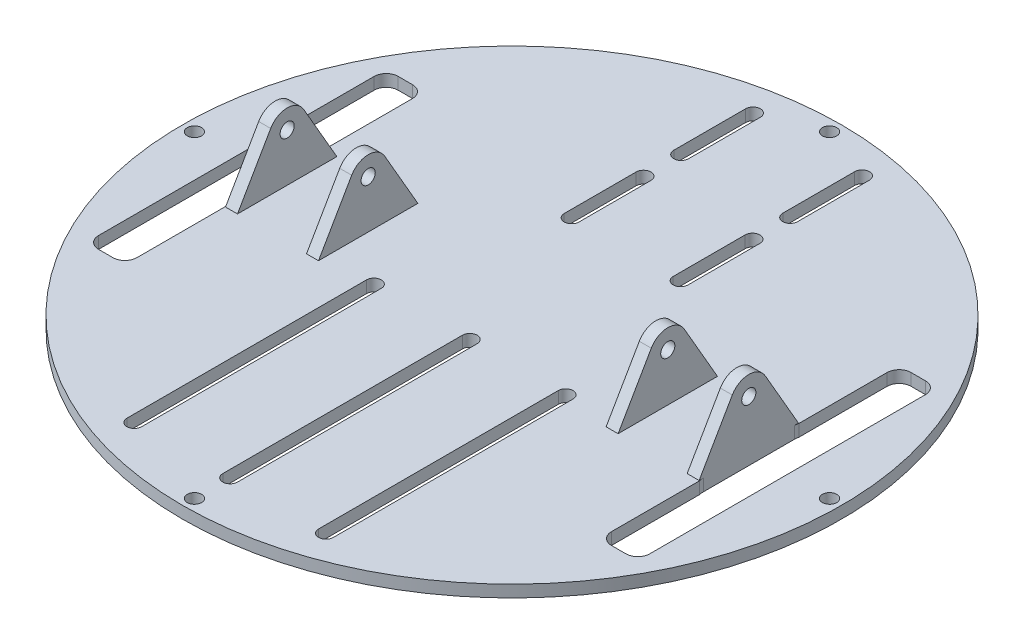
SolidWorks part; units mm, degrees
note: The reader was unsure of these and kept them because the rebuilt part matched: shared geometry of "Sketch6<2>", "Sketch6<3>", "Sketch6<4>", "Sketch17<3>".
material "ABS"
ref_plane "Front Plane" through (0, 0, 0) normal (0, 0, 1) x (1, 0, 0)
ref_plane "Top Plane" through (0, 0, 0) normal (0, 1, 0) x (1, 0, 0)
ref_plane "Right Plane" through (0, 0, 0) normal (1, 0, 0) x (0, 0, -1)
sketch "Sketch1" plane through (0, 0, 0) normal (0, 1, 0) x (1, 0, 0)
  circle A0 centre (0, 0) radius 69.85
  dimension "D1" = 139.7
extrude "Boss-Extrude1" add sketch "Sketch1" along normal blind 2.54
ref_plane "Plane1" through (0, 0, 25.4) normal (0, 0, 1) x (1, 0, 0)
ref_plane "Plane2" through (0, 0, 27.94) normal (0, 0, 1) x (1, 0, 0)
ref_plane "Plane3" through (0, 12.7, 0) normal (0, 1, 0) x (1, 0, 0)
sketch "Sketch2" plane through (0, 12.7, 0) normal (0, 1, 0) x (1, 0, 0)
  line L0 (-69.85, 0) -> (69.85, 0) construction
  circle A0 centre (0, 0) radius 69.85 construction
sketch "Sketch4" plane through (0, 2.54, 0) normal (0, 1, 0) x (1, 0, 0)
  line L0 (-57.6, 13.7677) -> (-57.7, 9.6319)
  line L5 (-57.7, -9.6319) -> (-57.6, -13.7677)
  line L7 (-57.6, -2.3717) -> (-57.6, 1.054)
  line L8 (-57.6, 11.8181) -> (-57.6, 13.7677)
  line L9 (-50.7, -9.6319) -> (-50.8, -13.7677)
  line L10 (-50.8, 13.7677) -> (-50.7, 9.6319)
  line L13 (-50.8, -12.7494) -> (-50.8, -13.7677)
  line L14 (-52.7, 12.3602) -> (-55.7, 12.3602)
  line L15 (-55.7, -12.3602) -> (-52.7, -12.3602)
  line L16 (-50.8, -8.1101) -> (-57.6, -8.1101)
  line L24 (-55.7, -12.3602) -> (-52.7, -12.3602)
  line L25 (-52.7, 12.3602) -> (-55.7, 12.3602)
  line L36 (50.8, 13.7677) -> (50.7, 9.6319)
  line L37 (50.7, -9.6319) -> (50.8, -13.7677)
  line L38 (57.6, -8.1101) -> (50.8, -8.1101)
  line L41 (50.8, 3.6498) -> (50.8, 9.5896)
  line L42 (50.8, 12.0156) -> (50.8, 13.7677)
  line L43 (57.7, -9.6319) -> (57.6, -13.7677)
  line L44 (57.6, 13.7677) -> (57.7, 9.6319)
  line L47 (50.8, 3.8982) -> (57.6, 3.8982)
  line L48 (57.6, -2.1606) -> (57.6, -5.4064)
  line L49 (57.6, -12.7494) -> (57.6, -13.7677)
  line L50 (55.7, 12.3602) -> (52.7, 12.3602)
  line L51 (52.7, -12.3602) -> (55.7, -12.3602)
  line L53 (50.8, 3.8982) -> (57.6, 3.8982)
  line L54 (57.6, -8.1101) -> (50.8, -8.1101)
  line L55 (-57.6, 7.9886) -> (-50.8, 7.9886)
  line L56 (-50.8, 6.3847) -> (-57.6, 6.3847)
  line L58 (-57.6, 1.8496) -> (-50.8, 1.8496)
  line L59 (-57.6, 1.8496) -> (-50.8, 1.8496)
  line L68 (52.7, -12.3602) -> (55.7, -12.3602)
  line L69 (55.7, 12.3602) -> (52.7, 12.3602)
  line L84 (50.7, 9.6319) -> (50.7, -9.6319)
  line L85 (57.7, 9.6319) -> (57.7, -9.6319)
  line L86 (-50.7, -9.6319) -> (-50.7, 9.6319)
  line L87 (-57.7, 9.6319) -> (-57.7, -9.6319)
  line L88 (-55.7, -12.8682) -> (-52.7, -12.8682)
  line L89 (-50.192, -9.6319) -> (-50.192, 9.6319)
  line L90 (-52.7, 12.8682) -> (-55.7, 12.8682)
  line L91 (-58.208, 9.6319) -> (-58.208, -9.6319)
  line L92 (52.7, -12.8682) -> (55.7, -12.8682)
  line L93 (58.208, 9.6319) -> (58.208, -9.6319)
  line L94 (55.7, 12.8682) -> (52.7, 12.8682)
  line L95 (50.192, 9.6319) -> (50.192, -9.6319)
  line L97 (-50.8, 6.3847) -> (-57.6, 6.3847)
  line L98 (-57.6, 7.9886) -> (-50.8, 7.9886)
  line L111 (-50.8, -8.1101) -> (-57.6, -8.1101)
  spline S0 degree 3 poles (-257.7843, -987.9514) (-61.0731, 23.5042) (-50.2909, -4.4805) (-50.7184, -10.0367) (-50.7422, -10.2277) (-50.7938, -10.5194) (-50.8991, -10.8964) (-51.1082, -11.3511) (-51.3917, -11.7508) (-51.7033, -12.0293) (-51.9855, -12.1959) (-52.2176, -12.2898) (-63.1032, -14.8874) (-67.3253, 100.199) (-918.2979, -513.0923) knots -4.526378 -4.526378 -4.526378 -4.526378 0.055429 0.108849 0.160228 0.209539 0.345987 0.472318 0.608681 0.735454 0.803707 0.870178 0.935409 9.580653 9.580653 9.580653 9.580653 only from (-50.7, -9.6319) to (-52.7, -12.3602)
  spline S1 degree 3 poles (-1044.9562, 136.5527) (-53.3911, -9.3021) (-57.3125, 12.9118) (-52.459, 12.3428) (-52.3396, 12.3194) (-52.2215, 12.2866) (-52.1051, 12.2445) (-51.9909, 12.1933) (-51.8793, 12.1332) (-51.6734, 12.0024) (-51.3926, 11.7519) (-51.1085, 11.3516) (-50.8989, 10.8964) (-50.7771, 10.4574) (-49.0107, -1.1804) (-97.3265, -45.88) (-775.7848, -679.0248) knots -3.740415 -3.740415 -3.740415 -3.740415 0.032186 0.064454 0.09688 0.129542 0.162511 0.195858 0.229647 0.263939 0.391041 0.527784 0.654106 0.790546 0.891198 10.361417 10.361417 10.361417 10.361417 only from (-52.7, 12.3602) to (-50.7, 9.6319)
  spline S2 degree 3 poles (936.5562, -136.5527) (-55.0089, 9.3021) (-51.0875, -12.9118) (-55.941, -12.3428) (-56.0604, -12.3194) (-56.1785, -12.2866) (-56.2949, -12.2445) (-56.4091, -12.1933) (-56.5207, -12.1332) (-56.7266, -12.0024) (-57.0074, -11.7519) (-57.2915, -11.3516) (-57.5011, -10.8964) (-57.6229, -10.4574) (-59.3893, 1.1804) (-11.0735, 45.88) (667.3848, 679.0248) knots -3.740415 -3.740415 -3.740415 -3.740415 0.032186 0.064454 0.09688 0.129542 0.162511 0.195858 0.229647 0.263939 0.391041 0.527784 0.654106 0.790546 0.891198 10.361417 10.361417 10.361417 10.361417 only from (-55.7, -12.3602) to (-57.7, -9.6319)
  spline S3 degree 3 poles (149.3843, 987.9514) (-47.3269, -23.5042) (-58.1091, 4.4805) (-57.6816, 10.0367) (-57.6578, 10.2277) (-57.6062, 10.5194) (-57.5009, 10.8964) (-57.2918, 11.3511) (-57.0083, 11.7508) (-56.6967, 12.0293) (-56.4145, 12.1959) (-56.1824, 12.2898) (-45.2968, 14.8874) (-41.0747, -100.199) (809.8979, 513.0923) knots -4.526378 -4.526378 -4.526378 -4.526378 0.055429 0.108849 0.160228 0.209539 0.345987 0.472318 0.608681 0.735454 0.803707 0.870178 0.935409 9.580653 9.580653 9.580653 9.580653 only from (-57.7, 9.6319) to (-55.7, 12.3602)
  spline S4 degree 3 poles (-57.7, 9.6319) (-57.7, 9.7053) (-57.6963, 9.8467) (-57.6816, 10.0367) (-57.6578, 10.2277) (-57.6062, 10.5194) (-57.5009, 10.8964) (-57.2918, 11.3511) (-57.0083, 11.7508) (-56.6967, 12.0293) (-56.4145, 12.1959) (-56.1824, 12.2898) (-55.9389, 12.3479) (-55.7794, 12.3602) (-55.7, 12.3602) knots 0 0 0 0 0.055429 0.108849 0.160228 0.209539 0.345987 0.472318 0.608681 0.735454 0.803707 0.870178 0.935409 1 1 1 1
  spline S5 degree 3 poles (-55.7, -12.3602) (-55.7395, -12.3602) (-55.8185, -12.3572) (-55.941, -12.3428) (-56.0604, -12.3194) (-56.1785, -12.2866) (-56.2949, -12.2445) (-56.4091, -12.1933) (-56.5207, -12.1332) (-56.7266, -12.0024) (-57.0074, -11.7519) (-57.2915, -11.3516) (-57.5011, -10.8964) (-57.6229, -10.4574) (-57.6859, -10.0428) (-57.7, -9.7757) (-57.7, -9.6319) knots 0 0 0 0 0.032186 0.064454 0.09688 0.129542 0.162511 0.195858 0.229647 0.263939 0.391041 0.527784 0.654106 0.790546 0.891198 1 1 1 1
  spline S6 degree 3 poles (-52.7, 12.3602) (-52.6605, 12.3602) (-52.5815, 12.3572) (-52.459, 12.3428) (-52.3396, 12.3194) (-52.2215, 12.2866) (-52.1051, 12.2445) (-51.9909, 12.1933) (-51.8793, 12.1332) (-51.6734, 12.0024) (-51.3926, 11.7519) (-51.1085, 11.3516) (-50.8989, 10.8964) (-50.7771, 10.4574) (-50.7141, 10.0428) (-50.7, 9.7757) (-50.7, 9.6319) knots 0 0 0 0 0.032186 0.064454 0.09688 0.129542 0.162511 0.195858 0.229647 0.263939 0.391041 0.527784 0.654106 0.790546 0.891198 1 1 1 1
  spline S7 degree 3 poles (-50.7, -9.6319) (-50.7, -9.7053) (-50.7037, -9.8467) (-50.7184, -10.0367) (-50.7422, -10.2277) (-50.7938, -10.5194) (-50.8991, -10.8964) (-51.1082, -11.3511) (-51.3917, -11.7508) (-51.7033, -12.0293) (-51.9855, -12.1959) (-52.2176, -12.2898) (-52.4611, -12.3479) (-52.6206, -12.3602) (-52.7, -12.3602) knots 0 0 0 0 0.055429 0.108849 0.160228 0.209539 0.345987 0.472318 0.608681 0.735454 0.803707 0.870178 0.935409 1 1 1 1
  spline S8 degree 3 poles (-149.3843, -987.9514) (47.3269, 23.5042) (58.1091, -4.4805) (57.6816, -10.0367) (57.6578, -10.2277) (57.6062, -10.5194) (57.5009, -10.8964) (57.2918, -11.3511) (57.0083, -11.7508) (56.6967, -12.0293) (56.4145, -12.1959) (56.1824, -12.2898) (45.2968, -14.8874) (41.0747, 100.199) (-809.8979, -513.0923) knots -4.526378 -4.526378 -4.526378 -4.526378 0.055429 0.108849 0.160228 0.209539 0.345987 0.472318 0.608681 0.735454 0.803707 0.870178 0.935409 9.580653 9.580653 9.580653 9.580653 only from (57.7, -9.6319) to (55.7, -12.3602)
  spline S9 degree 3 poles (-936.5562, 136.5527) (55.0089, -9.3021) (51.0875, 12.9118) (55.941, 12.3428) (56.0604, 12.3194) (56.1785, 12.2866) (56.2949, 12.2445) (56.4091, 12.1933) (56.5207, 12.1332) (56.7266, 12.0024) (57.0074, 11.7519) (57.2915, 11.3516) (57.5011, 10.8964) (57.6229, 10.4574) (59.3893, -1.1804) (11.0735, -45.88) (-667.3848, -679.0248) knots -3.740415 -3.740415 -3.740415 -3.740415 0.032186 0.064454 0.09688 0.129542 0.162511 0.195858 0.229647 0.263939 0.391041 0.527784 0.654106 0.790546 0.891198 10.361417 10.361417 10.361417 10.361417 only from (55.7, 12.3602) to (57.7, 9.6319)
  spline S10 degree 3 poles (1044.9562, -136.5527) (53.3911, 9.3021) (57.3125, -12.9118) (52.459, -12.3428) (52.3396, -12.3194) (52.2215, -12.2866) (52.1051, -12.2445) (51.9909, -12.1933) (51.8793, -12.1332) (51.6734, -12.0024) (51.3926, -11.7519) (51.1085, -11.3516) (50.8989, -10.8964) (50.7771, -10.4574) (49.0107, 1.1804) (97.3265, 45.88) (775.7848, 679.0248) knots -3.740415 -3.740415 -3.740415 -3.740415 0.032186 0.064454 0.09688 0.129542 0.162511 0.195858 0.229647 0.263939 0.391041 0.527784 0.654106 0.790546 0.891198 10.361417 10.361417 10.361417 10.361417 only from (52.7, -12.3602) to (50.7, -9.6319)
  spline S11 degree 3 poles (257.7843, 987.9514) (61.0731, -23.5042) (50.2909, 4.4805) (50.7184, 10.0367) (50.7422, 10.2277) (50.7938, 10.5194) (50.8991, 10.8964) (51.1082, 11.3511) (51.3917, 11.7508) (51.7033, 12.0293) (51.9855, 12.1959) (52.2176, 12.2898) (63.1032, 14.8874) (67.3253, -100.199) (918.2979, 513.0923) knots -4.526378 -4.526378 -4.526378 -4.526378 0.055429 0.108849 0.160228 0.209539 0.345987 0.472318 0.608681 0.735454 0.803707 0.870178 0.935409 9.580653 9.580653 9.580653 9.580653 only from (50.7, 9.6319) to (52.7, 12.3602)
  spline S12 degree 3 poles (50.7, 9.6319) (50.7, 9.7053) (50.7037, 9.8467) (50.7184, 10.0367) (50.7422, 10.2277) (50.7938, 10.5194) (50.8991, 10.8964) (51.1082, 11.3511) (51.3917, 11.7508) (51.7033, 12.0293) (51.9855, 12.1959) (52.2176, 12.2898) (52.4611, 12.3479) (52.6206, 12.3602) (52.7, 12.3602) knots 0 0 0 0 0.055429 0.108849 0.160228 0.209539 0.345987 0.472318 0.608681 0.735454 0.803707 0.870178 0.935409 1 1 1 1
  spline S13 degree 3 poles (52.7, -12.3602) (52.6605, -12.3602) (52.5815, -12.3572) (52.459, -12.3428) (52.3396, -12.3194) (52.2215, -12.2866) (52.1051, -12.2445) (51.9909, -12.1933) (51.8793, -12.1332) (51.6734, -12.0024) (51.3926, -11.7519) (51.1085, -11.3516) (50.8989, -10.8964) (50.7771, -10.4574) (50.7141, -10.0428) (50.7, -9.7757) (50.7, -9.6319) knots 0 0 0 0 0.032186 0.064454 0.09688 0.129542 0.162511 0.195858 0.229647 0.263939 0.391041 0.527784 0.654106 0.790546 0.891198 1 1 1 1
  spline S14 degree 3 poles (55.7, 12.3602) (55.7395, 12.3602) (55.8185, 12.3572) (55.941, 12.3428) (56.0604, 12.3194) (56.1785, 12.2866) (56.2949, 12.2445) (56.4091, 12.1933) (56.5207, 12.1332) (56.7266, 12.0024) (57.0074, 11.7519) (57.2915, 11.3516) (57.5011, 10.8964) (57.6229, 10.4574) (57.6859, 10.0428) (57.7, 9.7757) (57.7, 9.6319) knots 0 0 0 0 0.032186 0.064454 0.09688 0.129542 0.162511 0.195858 0.229647 0.263939 0.391041 0.527784 0.654106 0.790546 0.891198 1 1 1 1
  spline S15 degree 3 poles (57.7, -9.6319) (57.7, -9.7053) (57.6963, -9.8467) (57.6816, -10.0367) (57.6578, -10.2277) (57.6062, -10.5194) (57.5009, -10.8964) (57.2918, -11.3511) (57.0083, -11.7508) (56.6967, -12.0293) (56.4145, -12.1959) (56.1824, -12.2898) (55.9389, -12.3479) (55.7794, -12.3602) (55.7, -12.3602) knots 0 0 0 0 0.055429 0.108849 0.160228 0.209539 0.345987 0.472318 0.608681 0.735454 0.803707 0.870178 0.935409 1 1 1 1
  spline S16 degree 1 poles (-50.192, -9.6319) (-52.7, -12.8682) knots 0 0 1 1 construction
  spline S17 degree 1 poles (-52.7, 12.8682) (-50.192, 9.6319) knots 0 0 1 1 construction
  spline S18 degree 1 poles (-58.208, 9.6319) (-55.7, 12.8682) knots 0 0 1 1 construction
  spline S19 degree 1 poles (-55.7, -12.8682) (-58.208, -9.6319) knots 0 0 1 1 construction
  spline S20 degree 3 poles (-52.7, -12.8682) (-52.2962, -12.8682) (-51.4629, -12.5984) (-50.6751, -11.7167) (-50.2682, -10.6865) (-50.192, -9.9846) (-50.192, -9.6319) knots 0.000003 0.000003 0.000003 0.000003 0.250001 0.499999 0.749997 0.999995 0.999995 0.999995 0.999995
  spline S21 degree 3 poles (-50.192, 9.6319) (-50.192, 9.9852) (-50.2692, 10.6892) (-50.675, 11.7166) (-51.4641, 12.5992) (-52.2965, 12.8682) (-52.7, 12.8682) knots 0.000005 0.000005 0.000005 0.000005 0.250003 0.500001 0.749999 0.999997 0.999997 0.999997 0.999997
  spline S22 degree 3 poles (-55.7, 12.8682) (-56.1038, 12.8682) (-56.9371, 12.5984) (-57.7249, 11.7167) (-58.1318, 10.6865) (-58.208, 9.9846) (-58.208, 9.6319) knots 0.000003 0.000003 0.000003 0.000003 0.250001 0.499999 0.749997 0.999995 0.999995 0.999995 0.999995
  spline S23 degree 3 poles (-58.208, -9.6319) (-58.208, -9.9852) (-58.1308, -10.6892) (-57.725, -11.7166) (-56.9359, -12.5992) (-56.1035, -12.8682) (-55.7, -12.8682) knots 0.000005 0.000005 0.000005 0.000005 0.250003 0.500001 0.749999 0.999997 0.999997 0.999997 0.999997
  spline S24 degree 1 poles (58.208, -9.6319) (55.7, -12.8682) knots 0 0 1 1 construction
  spline S25 degree 1 poles (55.7, 12.8682) (58.208, 9.6319) knots 0 0 1 1 construction
  spline S26 degree 1 poles (50.192, 9.6319) (52.7, 12.8682) knots 0 0 1 1 construction
  spline S27 degree 1 poles (52.7, -12.8682) (50.192, -9.6319) knots 0 0 1 1 construction
  spline S28 degree 3 poles (55.7, -12.8682) (56.1038, -12.8682) (56.9371, -12.5984) (57.7249, -11.7167) (58.1318, -10.6865) (58.208, -9.9846) (58.208, -9.6319) knots 0.000003 0.000003 0.000003 0.000003 0.250001 0.499999 0.749997 0.999995 0.999995 0.999995 0.999995
  spline S29 degree 3 poles (58.208, 9.6319) (58.208, 9.9852) (58.1308, 10.6892) (57.725, 11.7166) (56.9359, 12.5992) (56.1035, 12.8682) (55.7, 12.8682) knots 0.000005 0.000005 0.000005 0.000005 0.250003 0.500001 0.749999 0.999997 0.999997 0.999997 0.999997
  spline S30 degree 3 poles (52.7, 12.8682) (52.2962, 12.8682) (51.4629, 12.5984) (50.6751, 11.7167) (50.2682, 10.6865) (50.192, 9.9846) (50.192, 9.6319) knots 0.000003 0.000003 0.000003 0.000003 0.250001 0.499999 0.749997 0.999995 0.999995 0.999995 0.999995
  spline S31 degree 3 poles (50.192, -9.6319) (50.192, -9.9852) (50.2692, -10.6892) (50.675, -11.7166) (51.4641, -12.5992) (52.2965, -12.8682) (52.7, -12.8682) knots 0.000005 0.000005 0.000005 0.000005 0.250003 0.500001 0.749999 0.999997 0.999997 0.999997 0.999997
  dimension "D1" = 0.508
extrude "Cut-Extrude1" cut sketch "Sketch4" against normal through all contours S7 L86 S6 L25 S4 L87 S5 L24 | L91 S23 L88 S20 L89 S21 L90 S22 L86 S7 L24 S5 L87 S4 L25 S6 | S15 L85 S14 L69 S12 L84 S13 L68 | L95 S31 L92 S28 L93 S29 L94 S30 L85 S15 L68 S13 L84 S12 L69 S14
sketch "Sketch6" plane through (0, 0, 0) normal (1, 0, 0) x (0, 0, -1)
  line L0 (3.4987, 14.72) -> (10.5309, 2.54)
  line L1 (9.6319, 2.54) -> (-9.6319, 2.54) construction
  line L2 (10.5309, 2.54) -> (-10.5309, 2.54)
  line L3 (-10.5309, 2.54) -> (-3.4987, 14.72)
  circle A0 centre (0, 12.7) radius 1.5
  arc A1 (-3.4987, 14.72) -> (3.4987, 14.72) centre (0, 12.7) cw
  dimension "D2" = 2.54
  dimension "D3" = 3
  dimension "D1" = 60
extrude "Boss-Extrude2" add sketch "Sketch6" against normal blind 2.54 from surface at 50.192 starting at face at (50.192, 1.27, 0)
extrude "Boss-Extrude3" add sketch "Sketch6<2>" along normal blind 2.54 from surface at -50.192 starting at face at (-50.192, 1.27, 0)
sketch "Sketch6<2>" plane through (0, 0, 0) normal (1, 0, 0) x (0, 0, -1) same geometry as "Sketch6"
extrude "Boss-Extrude4" add sketch "Sketch6<3>" along normal blind 2.54 from offset 30.48
sketch "Sketch6<3>" plane through (0, 0, 0) normal (1, 0, 0) x (0, 0, -1) same geometry as "Sketch6"
extrude "Boss-Extrude5" add sketch "Sketch6<4>" against normal blind 2.54 from offset 30.48 offset against normal yes
sketch "Sketch6<4>" plane through (0, 0, 0) normal (1, 0, 0) x (0, 0, -1) same geometry as "Sketch6"
sketch "Sketch7" plane through (0, 0, 0) normal (0, -1, 0) x (1, 0, 0)
  line L0 (0, 45.72) -> (0, 55.88)
  arc A0 (0, 55.88) -> (0, 45.72) centre (0, 50.8) cw
  dimension "D1" = 5.08
  dimension "D2" = 50.8
revolve "Revolve1" [suppressed] add sketch "Sketch7" angle 180 about L0
mirror "Mirror1" [suppressed] about plane through (0, 0, 0) normal (0, 0, 1)
sketch "Sketch8" plane through (0, 2.54, 0) normal (0, 1, 0) x (1, 0, 0)
  line L0 (0, -9.207) -> (0, 9.207) construction
  line L1 (-55.88, -31.75) -> (-52.832, -31.75)
  line L2 (-58.42, -29.21) -> (-58.42, 29.21)
  line L3 (-55.88, 31.75) -> (-52.832, 31.75)
  line L4 (-50.292, -29.21) -> (-50.292, 29.21)
  line L5 (50.292, -29.21) -> (50.292, 29.21)
  line L6 (55.88, 31.75) -> (52.832, 31.75)
  line L7 (58.42, -29.21) -> (58.42, 29.21)
  line L8 (55.88, -31.75) -> (52.832, -31.75)
  arc A0 (-55.88, 31.75) -> (-58.42, 29.21) centre (-55.88, 29.21) ccw
  arc A1 (-50.292, 29.21) -> (-52.832, 31.75) centre (-52.832, 29.21) ccw
  arc A2 (-50.292, -29.21) -> (-52.832, -31.75) centre (-52.832, -29.21) cw
  arc A3 (-55.88, -31.75) -> (-58.42, -29.21) centre (-55.88, -29.21) cw
  arc A4 (55.88, -31.75) -> (58.42, -29.21) centre (55.88, -29.21) ccw
  arc A5 (50.292, -29.21) -> (52.832, -31.75) centre (52.832, -29.21) ccw
  arc A6 (50.292, 29.21) -> (52.832, 31.75) centre (52.832, 29.21) cw
  arc A7 (55.88, 31.75) -> (58.42, 29.21) centre (55.88, 29.21) cw
  point P7 (-58.42, 31.75)
  point P12 (-50.292, -31.75)
  point P15 (-58.42, -31.75)
  point P30 (58.42, -31.75)
  point P31 (50.292, -31.75)
  point P32 (58.42, 31.75)
  dimension "D5" = 2.54
  dimension "D1" = 8.128
  dimension "D2" = 63.5
  dimension "D3" = 50.292
  dimension "D4" = 31.75
extrude "Cut-Extrude2" cut sketch "Sketch8" against normal blind 2.54
sketch "Sketch15" plane through (0, 0, 0) normal (0, -1, 0) x (1, 0, 0)
  circle A0 centre (67.31, 0) radius 1.524
  circle A1 centre (0, -67.31) radius 1.524
  circle A2 centre (-67.31, 0) radius 1.524
  circle A3 centre (0, 67.31) radius 1.524
  dimension "D1" = 67.31
  dimension "D2" = 3.048
  dimension "D4" = 67.31
  dimension "D5" = 67.31
  dimension "D3" = 4
extrude "Cut-Extrude3" cut sketch "Sketch15" against normal through all
sketch "Sketch16" plane through (0, 2.54, 0) normal (0, 1, 0) x (1, 0, 0)
  line L0 (9.9899, 24.1825) -> (9.9899, 39.4225)
  line L1 (13.1149, 24.1825) -> (13.1149, 39.4225)
  line L2 (25.5, 22.62) -> (-25.5, 22.62) construction
  line L3 (11.5524, 24.1825) -> (11.5524, 29.5324) construction
  line L4 (9.9899, 47.4021) -> (9.9899, 62.6421)
  line L5 (13.1149, 47.4021) -> (13.1149, 62.6421)
  line L6 (11.5524, 47.4021) -> (11.5524, 52.752) construction
  line L7 (0, -9.207) -> (0, 9.207) construction
  line L8 (-13.1149, 47.4021) -> (-13.1149, 62.6421)
  line L9 (-9.9899, 47.4021) -> (-9.9899, 62.6421)
  line L10 (-9.9899, 24.1825) -> (-9.9899, 39.4225)
  line L11 (-13.1149, 24.1825) -> (-13.1149, 39.4225)
  arc A0 (13.1149, 24.1825) -> (9.9899, 24.1825) centre (11.5524, 24.1825) cw
  arc A1 (9.9899, 39.4225) -> (13.1149, 39.4225) centre (11.5524, 39.4225) cw
  circle A2 centre (11.5524, 29.6473) radius 1.5625 construction
  arc A3 (13.1149, 47.4021) -> (9.9899, 47.4021) centre (11.5524, 47.4021) cw
  arc A4 (9.9899, 62.6421) -> (13.1149, 62.6421) centre (11.5524, 62.6421) cw
  circle A5 centre (11.5524, 52.752) radius 1.5625 construction
  arc A6 (-9.9899, 62.6421) -> (-13.1149, 62.6421) centre (-11.5524, 62.6421) ccw
  arc A7 (-13.1149, 47.4021) -> (-9.9899, 47.4021) centre (-11.5524, 47.4021) ccw
  arc A8 (-9.9899, 39.4225) -> (-13.1149, 39.4225) centre (-11.5524, 39.4225) ccw
  arc A9 (-13.1149, 24.1825) -> (-9.9899, 24.1825) centre (-11.5524, 24.1825) ccw
  dimension "D1" = 15.24
  dimension "D2" = 15.24
extrude "Cut-Extrude4" cut sketch "Sketch16" against normal through all
sketch "Sketch17" plane through (0, 2.54, 0) normal (0, 1, 0) x (1, 0, 0)
  line L0 (-1.5625, -8.9425) -> (-1.5625, -59.7425)
  line L1 (1.5625, -8.9425) -> (1.5625, -59.7425)
  line L2 (21.8825, -8.9425) -> (21.8825, -59.7425)
  line L3 (18.7575, -8.9425) -> (18.7575, -59.7425)
  line L6 (-25.5, -7.38) -> (25.5, -7.38) construction
  arc A0 (-1.5625, -8.9425) -> (1.5625, -8.9425) centre (0, -8.9425) cw
  arc A1 (-1.5625, -59.7425) -> (1.5625, -59.7425) centre (0, -59.7425) ccw
  circle A2 centre (-24.27, -29.21) radius 1.5625 construction
  arc A3 (18.7575, -8.9425) -> (21.8825, -8.9425) centre (20.32, -8.9425) cw
  arc A4 (18.7575, -59.7425) -> (21.8825, -59.7425) centre (20.32, -59.7425) ccw
  point P6 (-76.811, 2.54)
  point P10 (-76.811, -20.7508)
  point P19 (0, 0)
  point P20 (0, 0)
  point P21 (0, 0)
  dimension "D1" = 50.8
  dimension "D2" = 20.32
extrude "Cut-Extrude5" cut sketch "Sketch17" against normal through all contours L3 A4 L2 A3
mirror "Mirror2" about plane through (0, 0, 0) normal (1, 0, 0) of "Cut-Extrude5"
extrude "Cut-Extrude6" cut sketch "Sketch17<3>" against normal through all contours L0 A1 L1 A0
sketch "Sketch17<3>" plane through (0, 2.54, 0) normal (0, 1, 0) x (1, 0, 0) same geometry as "Sketch17"
